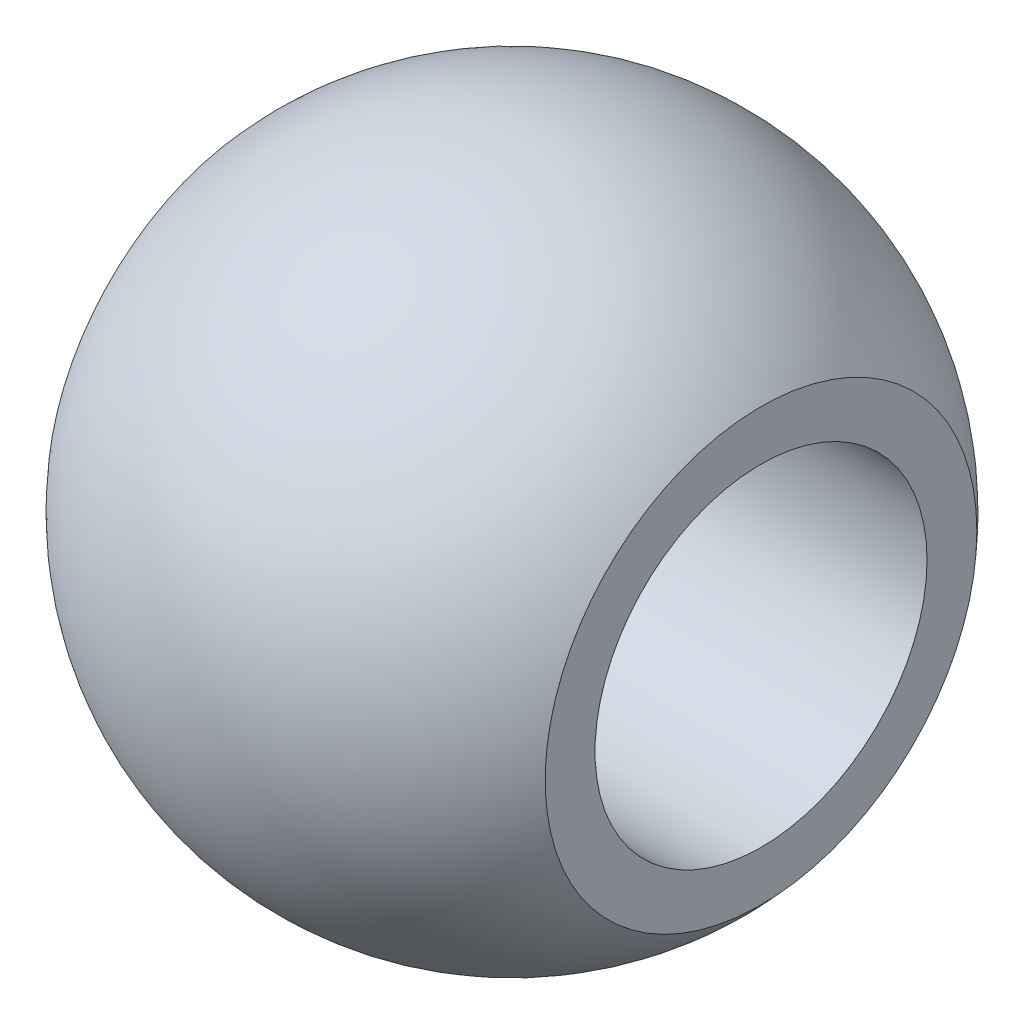
SolidWorks part; units mm, degrees
material "AISI 1020"
ref_plane "Front Plane" through (0, 0, 0) normal (0, 0, 1) x (1, 0, 0)
ref_plane "Top Plane" through (0, 0, 0) normal (0, 1, 0) x (1, 0, 0)
ref_plane "Right Plane" through (0, 0, 0) normal (1, 0, 0) x (0, 0, -1)
sketch "Sketch1" plane through (0, 0, 0) normal (0, 1, 0) x (1, 0, 0)
  line L0 (6, 0) -> (-6, 0) construction
  line L1 (6, 4) -> (-6, 4)
  line L2 (-6, 4) -> (-6, 5.2003)
  line L3 (6, 4) -> (6, 5.2003)
  arc A0 (-6, 5.2003) -> (6, 5.2003) centre (0, 0) cw
  dimension "D3" = 7.94
  dimension "D1" = 12
  dimension "D2" = 4
revolve "Revolve1" add sketch "Sketch1" angle 360 about L0
ref_axis "Axis1" through (-6.064, 0, 0) along (1, 0, 0)
